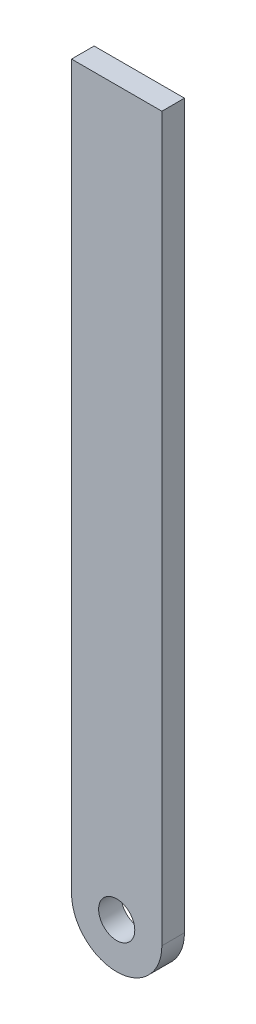
SolidWorks part; units mm, degrees
ref_plane "Front" through (0, 0, 0) normal (0, 0, 1) x (1, 0, 0)
ref_plane "Top" through (0, 0, 0) normal (0, 1, 0) x (1, 0, 0)
ref_plane "Right" through (0, 0, 0) normal (1, 0, 0) x (0, 0, -1)
sketch "Esquisse1" plane through (0, 0, 0) normal (0, 0, 1) x (1, 0, 0)
  line L1 (0, 0) -> (20, 0)
  line L2 (0, 0) -> (0, 170)
  line L3 (0, 170) -> (20, 170)
  line L4 (20, 0) -> (20, 170)
  dimension "D1" = 20
  dimension "D2" = 170
extrude "Boss.-Extru.1" add sketch "Esquisse1" along normal blind 5
sketch "Esquisse2" plane through (0, 0, 5) normal (0, 0, 1) x (1, 0, 0)
  line L0 (10, 0) -> (10, 10) construction
  line L1 (0, 0) -> (20, 0) construction
  line L2 (10, 10) -> (0, 10) construction
  line L3 (0, 170) -> (0, 0) construction
  circle A0 centre (10, 10) radius 4
  dimension "D2" = 8
  dimension "D1" = 10
extrude "Enlèv. mat.-Extru.1" cut sketch "Esquisse2" against normal through all both and the other way through all
fillet "Congé1" radius 10 2 edges at (20, 0, 2.5) (0, 0, 2.5)
